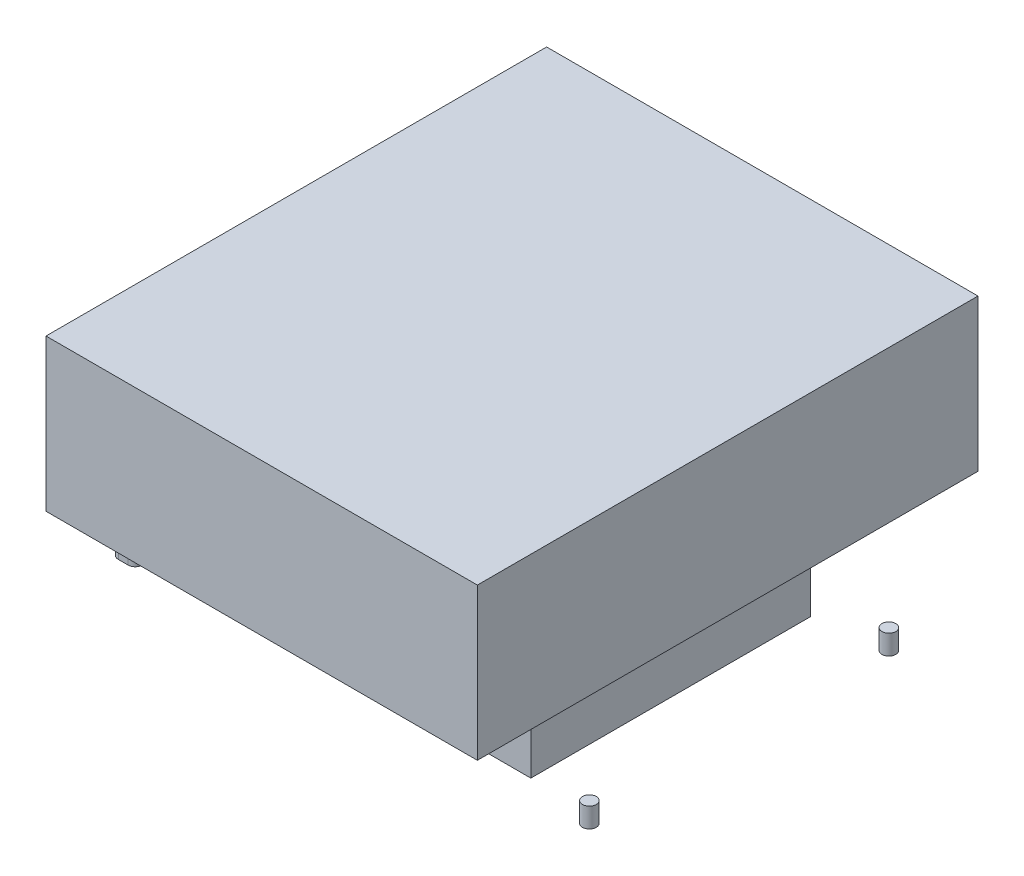
SolidWorks part; units mm, degrees
ref_plane "Front Plane" through (0, 0, 0) normal (0, 0, 1) x (1, 0, 0)
ref_plane "Top Plane" through (0, 0, 0) normal (0, 1, 0) x (1, 0, 0)
ref_plane "Right Plane" through (0, 0, 0) normal (1, 0, 0) x (0, 0, -1)
sketch "Sketch1" plane through (0, 0, 0) normal (0, 1, 0) x (1, 0, 0)
  line L0 (114.5, 75.5) -> (114.5, -75.5) construction
  line L1 (-80, -70.5) -> (80, -70.5)
  line L2 (-80, -70.5) -> (-80, 70.5)
  line L3 (-80, 70.5) -> (80, 70.5)
  line L4 (80, -70.5) -> (80, 70.5)
  line L5 (-80, -70.5) -> (80, 70.5) construction
  line L6 (-80, 70.5) -> (80, -70.5) construction
  line L7 (-108.7438, -126.2062) -> (108.7438, -126.2062)
  line L8 (-108.7438, -126.2062) -> (-108.7438, 126.2063)
  line L9 (-108.7438, 126.2063) -> (108.7438, 126.2063)
  line L10 (108.7438, -126.2062) -> (108.7438, 126.2063)
  line L11 (-108.7438, -126.2062) -> (108.7438, 126.2063) construction
  line L12 (-108.7438, 126.2063) -> (108.7438, -126.2062) construction
  line L13 (-119.5, -79) -> (-114.5, -79)
  line L14 (-119.5, 72) -> (-114.5, 72)
  line L16 (-119.5, 79) -> (-114.5, 79)
  line L18 (-119.5, -72) -> (-114.5, -72)
  line L19 (-123, -75.5) -> (-111, -75.5) construction
  line L20 (-119.5, -72) -> (-119.5, -79) construction
  line L21 (-114.5, -72) -> (-114.5, -79) construction
  line L22 (-123, 75.5) -> (-111, 75.5) construction
  line L23 (-111, 75.5) -> (111, 75.5) construction
  circle A0 centre (114.5, 75.5) radius 3.5
  circle A1 centre (114.5, -75.5) radius 3.5
  arc A2 (-119.5, 79) -> (-119.5, 72) centre (-119.5, 75.5) ccw
  arc A3 (-114.5, 79) -> (-114.5, 72) centre (-114.5, 75.5) cw
  arc A4 (-119.5, -72) -> (-119.5, -79) centre (-119.5, -75.5) ccw
  arc A5 (-114.5, -72) -> (-114.5, -79) centre (-114.5, -75.5) cw
  point P0 (0, 0)
  point P6 (0, 0)
  point P15 (108.7438, 0)
  point P16 (114.5, 0)
  point P17 (-117, 75.5)
  point P32 (-117, -75.5)
  point P33 (0, 75.5)
  point P35 (0, 126.2062)
  point P36 (-119.5, 72)
  point P37 (0, 0)
  point P38 (114.5, -75.5)
  dimension "D5" = 7
  dimension "D8" = 3.5
  dimension "D11" = 3.5
  dimension "D1" = 160
  dimension "D2" = 141
  dimension "D3" = 217.4875
  dimension "D4" = 252.4125
  dimension "D6" = 151
  dimension "D7" = 5
  dimension "D9" = 7
  dimension "D10" = 5
  dimension "D12" = 7
  dimension "D13" = 222
extrude "Boss-Extrude1" add sketch "Sketch1" along normal blind 50 contours L1 L4 L3 L2 region at (0, 0, 0)
extrude "Boss-Extrude2" add sketch "Sketch1<3>" along normal blind 76.5302 from surface contours L10 L9 L8 L7 starting at face at (0, 50, 0)
sketch "Sketch1<3>" plane through (0, 0, 0) normal (0, 1, 0) x (1, 0, 0) same geometry as "Sketch1"
extrude "Boss-Extrude3" add sketch "Sketch1<4>" along normal blind 10 separate body contours A3 L16 A2 L14 | A5 L18 A4 L13 | A1 | A0 region at (-117, 0, 75.5) region at (-117, 0, -75.5) region at (114.5, 0, 75.5)
sketch "Sketch1<4>" plane through (0, 0, 0) normal (0, 1, 0) x (1, 0, 0) same geometry as "Sketch1"
